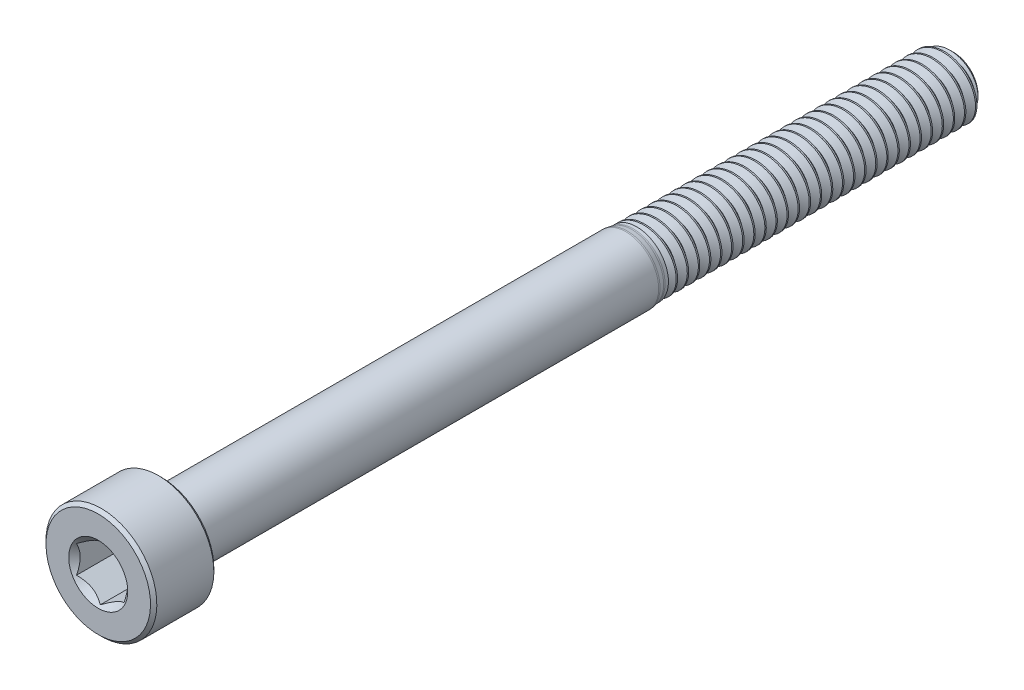
SolidWorks part; units mm, degrees
ref_plane "Front Plane" through (0, 0, 0) normal (0, 0, 1) x (1, 0, 0)
ref_plane "Top Plane" through (0, 0, 0) normal (0, 1, 0) x (1, 0, 0)
ref_plane "Right Plane" through (0, 0, 0) normal (1, 0, 0) x (0, 0, -1)
sketch "Sketch1" plane through (0, 0, 0) normal (1, 0, 0) x (0, 0, -1)
  line L0 (-27, 0) -> (27, 0) construction
  line L1 (27, 0) -> (27, 1.5453) construction
  line L2 (27, 1.5453) -> (26.5453, 2) construction
  line L3 (26.5453, 2) -> (26.475, 2) construction
  line L4 (26.475, 2) -> (-23, 2) construction
  line L5 (-23, 2) -> (-23, 3.5) construction
  line L6 (-23, 3.5) -> (-27, 3.5) construction
  line L7 (-27, 3.5) -> (-27, 0) construction
  line L8 (27, 1.5453) -> (27, 2) construction
  line L9 (26.9563, 2.0758) -> (27.3063, 1.4696) construction
  line L10 (27.3063, 1.4696) -> (27.6563, 2.0758) construction
  line L11 (27.6563, 2.0758) -> (26.9563, 2.0758) construction
  line L12 (27.3063, 2.0758) -> (27.3063, 2) construction
  line L13 (27.3063, 1.4696) -> (27.3063, 1.5453) construction
  line L14 (27.2625, 1.5453) -> (27.35, 1.5453) construction
  line L15 (27, 2) -> (27.6125, 2) construction
  line L16 (26.9781, 2.0379) -> (27.6344, 2.0379) construction
  line L17 (27, 0) -> (27, -2) construction
  line L18 (-23.2, 3.5) -> (-23, 3.3) construction
  line L19 (-26.8, 3.5) -> (-27, 3.3) construction
  line L20 (-23, 2) -> (-23, 0) construction
  line L21 (-23, 1) -> (-6.3333, 1) construction
  line L22 (-6.3333, 1) -> (10.3333, 1) construction
  line L23 (10.3333, 1) -> (27, 1) construction
  line L24 (-6.3333, 1) -> (-6.3333, 2) construction
  line L25 (-6.3333, 2) -> (-6.3333, 3.5) construction
  line L26 (10.3333, 1) -> (10.3333, 3.5) construction
  point P0 (-27, 1.5)
  point P3 (25.25, 2)
  point P4 (0, 0)
  point P18 (10.3333, 2)
  point P22 (27.3063, 1.5453)
  point P24 (26.475, 2)
  point P25 (27.3063, 2)
  point P28 (27.3063, 2.0379)
  point P29 (25.25, -2)
  point P30 (-6.3333, 2)
  point P31 (-25, 3.5)
  point P37 (-23.7, 3.5)
  point P38 (-26.7, 3.5)
  point P45 (-6.3333, 1)
  point P46 (10.3333, 1)
  point P49 (7, 2)
  dimension "D1" = 45
  dimension "D2" = 0.0875
  dimension "D7" = 0.2
  dimension "D8" = 0.2
  dimension "D9" = 0.2
  dimension "D10" = 0.1
  dimension "D11" = 0.5
  dimension "Drive Size" = 3
  dimension "Head Diameter" = 7
  dimension "Head Height" = 4
  dimension "Thread Pitch" = 0.7
  dimension "Thread Dia" = 4
  dimension "Length" = 50
  dimension "D12" = 0.525
  dimension "D4" = 1.75
  dimension "Minimum Thread Length" = 20
  dimension "D3" = 30
sketch "Sketch2" plane through (0, 0, 0) normal (1, 0, 0) x (0, 0, -1)
  line L0 (-27, 0) -> (-27, 3.3)
  line L1 (-26.8, 3.5) -> (-23.2, 3.5)
  line L2 (-23, 3.3) -> (-23, 2.2758)
  line L4 (26.5453, 2) -> (27, 1.5453)
  line L5 (27, 1.5453) -> (27, 0)
  line L6 (-23, 3.5) -> (-27, 3.5) construction
  line L7 (27, 0) -> (-27, 0)
  line L8 (-26.8, 3.5) -> (-27, 3.3) construction
  line L10 (-26.8, 3.5) -> (-27, 3.3)
  line L14 (-23.2, 3.5) -> (-23, 3.3) construction
  line L16 (-23.2, 3.5) -> (-23, 3.3)
  line L17 (-23, 2) -> (-23, 3.5) construction
  line L18 (-22.8, 2.0758) -> (6.3073, 2.0758)
  line L19 (6.7867, 2) -> (26.5453, 2)
  line L20 (26.475, 2) -> (-23, 2) construction
  line L21 (6.4048, 2.0662) -> (6.6892, 2.0096)
  line L22 (27.6563, 2.0758) -> (26.9563, 2.0758) construction
  arc A1 (-23, 2.2758) -> (-22.8, 2.0758) centre (-22.8, 2.2758) ccw
  arc A2 (6.3073, 2.0758) -> (6.4048, 2.0662) centre (6.3073, 1.5758) cw
  arc A3 (6.6892, 2.0096) -> (6.7867, 2) centre (6.7867, 2.5) ccw
  point P39 (6.7375, 2)
  dimension "D3" = 0.2
  dimension "D6" = 0.5
  dimension "D4" = 11.25
  dimension "D5" = 0.2625
revolve "Revolve1" add sketch "Sketch2" angle 360 about L7
sketch "Sketch3" plane through (0, 0, 27) normal (0, 0, 1) x (1, 0, 0)
  line L1 (1.5, -0.866) -> (1.5, 0.866)
  line L2 (1.5, 0.866) -> (0, 1.7321)
  line L3 (0, 1.7321) -> (-1.5, 0.866)
  line L4 (-1.5, 0.866) -> (-1.5, -0.866)
  line L5 (-1.5, -0.866) -> (0, -1.7321)
  line L6 (0, -1.7321) -> (1.5, -0.866)
  circle A0 centre (0, 0) radius 1.5 construction
  circle A1 centre (0, 0) radius 3.5 construction
  circle A2 centre (0, 0) radius 3.5 construction
  circle A3 centre (0, 0) radius 1.7321 construction
  dimension "D1" = 3.4641
extrude "Cut-Extrude1" cut sketch "Sketch3" against normal offset from surface (3 mm away) 1 up to face at (0, 3.3, 23)
sketch "Sketch4" plane through (0, 0, 27) normal (0, 0, 1) x (1, 0, 0)
  circle A0 centre (0, 0) radius 1.862
  dimension "D1" = 3.7239
extrude "Cut-Extrude2" cut sketch "Sketch4" against normal up to vertex (2 mm away) draft 45 up to point (0, 3.5, 25)
sketch "Sketch11" plane through (0, 0, 0) normal (1, 0, 0) x (0, 0, -1)
  line L0 (-27, 0) -> (27, 0) construction
  line L1 (-27, 0) -> (27, 0) construction
  line L2 (-20.375, 0) -> (-20.375, 2) construction
  line L3 (26.475, 2) -> (-23, 2) construction
  line L4 (3.6823, 0) -> (3.6823, 2) construction
  point P2 (-20.375, 0)
  point P3 (3.6823, 0)
  dimension "D1" = 2.625
  dimension "D2" = 2.625
sketch "Sketch6" plane through (0, 0, -27) normal (0, 0, -1) x (-1, 0, 0)
  circle A0 centre (0, 0) radius 2
curve "Helix/Spiral1" pitch 0.7 height 20.7 radius 2 centre (0, 0, -27) axis (0, 0, 1) start towards (0, 1, 0)
sketch "Sketch10" plane through (0, 0, 0) normal (1, 0, 0) x (0, 0, -1)
  line L0 (7, -2) -> (7, 2)
  line L2 (-27, 0) -> (27, 0) construction
  point P3 (7, 0)
split "Split1" trim tools "Sketch10" bodies to split 106 resulting bodies 114 115
sketch "Sketch7" plane through (0, 0, 0) normal (1, 0, 0) x (0, 0, -1)
  line L0 (26.9781, 2.0379) -> (27.6344, 2.0379)
  line L1 (27.6344, 2.0379) -> (27.35, 1.5453)
  line L2 (27.35, 1.5453) -> (27.2625, 1.5453)
  line L3 (27.2625, 1.5453) -> (26.9781, 2.0379)
sweep "Cut-Sweep1" cut profiles "Sketch7" path "Helix/Spiral1" align with end faces yes
sketch "Sketch8" plane through (0, 0, 0) normal (1, 0, 0) x (0, 0, -1)
  line L0 (-23, 0) -> (-23, 2)
  line L2 (-23, 2) -> (7, 2)
  line L4 (7, 2) -> (8.1547, 0)
  line L5 (8.1547, 0) -> (-23, 0)
  line L6 (26.475, 2) -> (-23, 2) construction
  line L7 (-27, 0) -> (27, 0) construction
  dimension "D1" = 60
  dimension "D2" = 20
revolve "Revolve2" add sketch "Sketch8" angle 360 about L5
ref_axis "Axis1" through (0, 0, 22.8) along (0, 0, -1)
equation "\"D2@Sketch1\" = \"Thread Pitch@Sketch1\" / 8"
equation "\"D4@Helix/Spiral1\" = \"Thread Pitch@Sketch1\""
equation "\"D7@Sketch1\" = \"Head Height@Sketch1\" * .05"
equation "\"D8@Sketch1\"=\"D7@Sketch1\""
equation "\"D9@Sketch1\"=\"D7@Sketch1\""
equation "\"D10@Sketch1\"=\"D7@Sketch1\"/2"
equation "\"D11@Sketch1\"=\"D10@Sketch1\"*5"
equation "\"D4@Sketch1\"=\"Thread Pitch@Sketch1\"*2.5"
equation "\"D12@Sketch1\"=\"Thread Pitch@Sketch1\"*.75"
equation "\"D3@Helix/Spiral1\"=\"Minimum Thread Length@Sketch1\"+\"Thread Pitch@Sketch1\""
equation "\"D2@Sketch8\"=\"Minimum Thread Length@Sketch1\""
equation "\"D3@Sketch2\"=\"Thread Dia@Sketch1\"*0.05"
equation "\"D5@Sketch2\"=\"D12@Sketch1\"*0.5"
equation "\"D6@Sketch2\"=\"Thread Dia@Sketch1\"*0.125"
equation "\"D1@Sketch11\"=\"D3@Sketch1\"*0.0875"
equation "\"D2@Sketch11\"=\"D1@Sketch11\""
equation "\"D1@Sketch4\"=\"D1@Sketch3\"*1.075"
